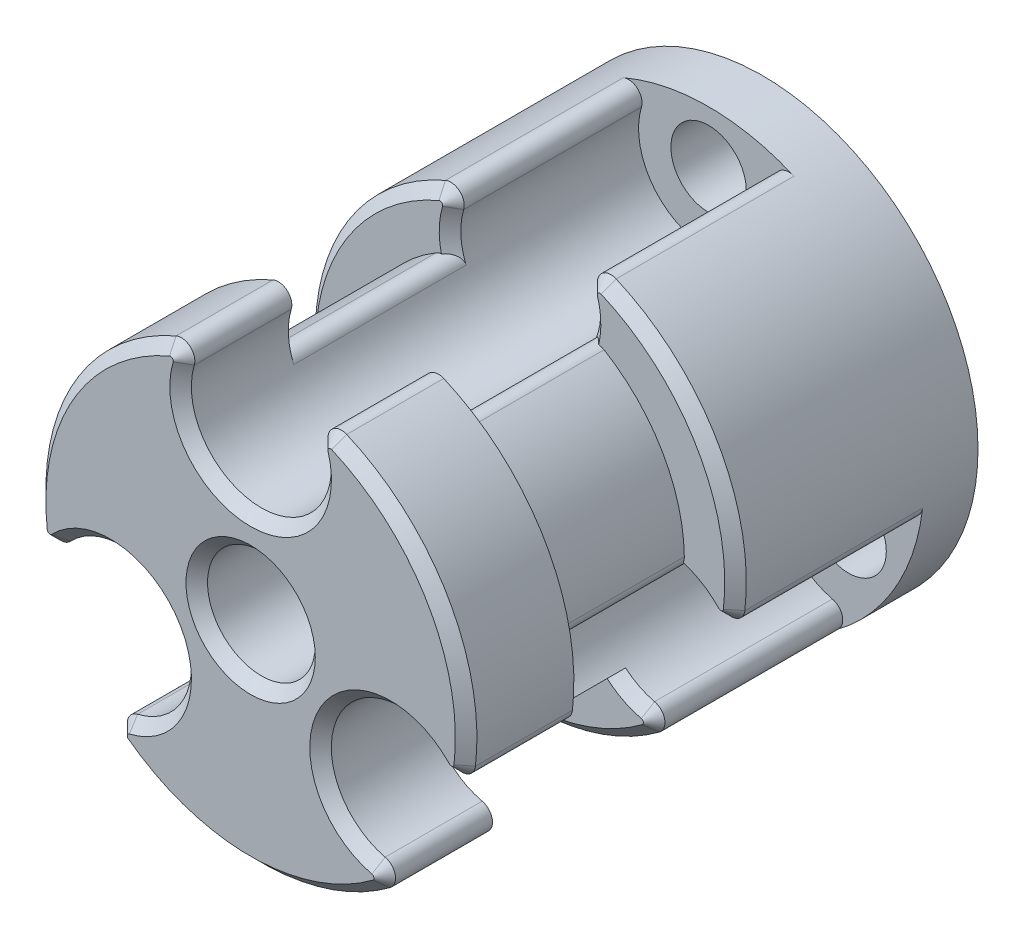
SolidWorks part; units mm, degrees
ref_plane "前视基准面" through (0, 0, 0) normal (0, 0, 1) x (1, 0, 0)
ref_plane "上视基准面" through (0, 0, 0) normal (0, 1, 0) x (1, 0, 0)
ref_plane "右视基准面" through (0, 0, 0) normal (1, 0, 0) x (0, 0, -1)
other "Configuration Table"
sketch "Sketch2" plane through (0, 0, 0) normal (0, 0, 1) x (1, 0, 0)
  circle A0 centre (0, 0) radius 8
  circle A1 centre (0, 0) radius 2
  circle A3 centre (0, 6) radius 1.4
  circle A5 centre (5.1962, -3) radius 1.4
  circle A6 centre (-5.1962, -3) radius 1.4
  point P11 (0, 0)
  dimension "D1" = 16
  dimension "D2" = 4
  dimension "D3" = 2.8
  dimension "D4" = 6
  dimension "D5" = 3
extrude "Boss-Extrude1" add sketch "Sketch2" along normal blind 9
sketch "Sketch3" plane through (0, 0, 9) normal (0, 0, 1) x (1, 0, 0)
  circle A0 centre (0, 6) radius 2.6
  circle A1 centre (5.1962, -3) radius 2.6
  circle A2 centre (-5.1962, -3) radius 2.6
  point P8 (0, 0)
  dimension "D1" = 5.2
  dimension "D2" = 3
extrude "Cut-Extrude1" cut sketch "Sketch3" against normal blind 7
fillet "Fillet1" radius 0.5 6 edges at (1.9045, 7.77, 5.5) (-1.9045, 7.77, 5.5) (-5.7768, -5.5343, 5.5) (-7.6813, -2.2357, 5.5) (5.7768, -5.5343, 5.5) (7.6813, -2.2357, 5.5)
sketch "Sketch4" plane through (0, 0, 9) normal (0, 0, 1) x (1, 0, 0)
  arc A0 (6.0749, -0.553) -> (2.5585, 5.5375) centre (0, 0) ccw
  arc A1 (-2.4914, 6.7437) -> (2.4914, 6.7437) centre (0, 6) ccw construction
  arc A2 (-4.5945, -5.5294) -> (-7.0859, -1.2142) centre (-5.1962, -3) ccw construction
  arc A3 (7.0859, -1.2142) -> (4.5945, -5.5294) centre (5.1962, -3) ccw construction
  arc A4 (-2.5585, 5.5375) -> (2.5585, 5.5375) centre (0, 6) ccw
  arc A5 (-3.5163, -4.9845) -> (-6.0749, -0.553) centre (-5.1962, -3) ccw
  arc A6 (6.0749, -0.553) -> (3.5163, -4.9845) centre (5.1962, -3) ccw
  arc A7 (-3.5163, -4.9845) -> (3.5163, -4.9845) centre (0, 0) ccw
  arc A8 (-2.5585, 5.5375) -> (-6.0749, -0.553) centre (0, 0) ccw
  circle A9 centre (0, 0) radius 2
  dimension "D1" = 12.2
extrude "Boss-Extrude2" add sketch "Sketch4" along normal blind 6
sketch "Sketch5" plane through (0, 0, 15) normal (0, 0, 1) x (1, 0, 0)
  arc A0 (7.9459, -0.9289) -> (3.1685, 7.3458) centre (0, 0) ccw
  arc A1 (-4.5945, -5.5294) -> (-4.7774, -6.4169) centre (-4.4788, -6.0159) ccw construction
  arc A2 (-4.5945, -5.5294) -> (-3.5163, -4.9845) centre (-5.1962, -3) ccw construction
  arc A3 (-3.5163, -4.9845) -> (-6.0749, -0.553) centre (-5.1962, -3) ccw construction
  arc A4 (-6.0749, -0.553) -> (-7.0859, -1.2142) centre (-5.1962, -3) ccw construction
  arc A5 (-7.9459, -0.9289) -> (-7.0859, -1.2142) centre (-7.4493, -0.8708) ccw construction
  arc A6 (-2.4914, 6.7437) -> (-3.1685, 7.3458) centre (-2.9705, 6.8867) ccw construction
  arc A7 (-2.4914, 6.7437) -> (-2.5585, 5.5375) centre (0, 6) ccw construction
  arc A8 (3.1685, 7.3458) -> (2.4914, 6.7437) centre (2.9705, 6.8867) ccw construction
  arc A9 (2.5585, 5.5375) -> (2.4914, 6.7437) centre (0, 6) ccw construction
  arc A10 (-2.5585, 5.5375) -> (2.5585, 5.5375) centre (0, 6) ccw construction
  arc A11 (7.0859, -1.2142) -> (6.0749, -0.553) centre (5.1962, -3) ccw construction
  arc A12 (7.0859, -1.2142) -> (7.9459, -0.9289) centre (7.4493, -0.8708) ccw construction
  arc A13 (3.5163, -4.9845) -> (4.5945, -5.5294) centre (5.1962, -3) ccw construction
  arc A14 (6.0749, -0.553) -> (3.5163, -4.9845) centre (5.1962, -3) ccw construction
  arc A15 (4.7774, -6.4169) -> (4.5945, -5.5294) centre (4.4788, -6.0159) ccw construction
  arc A16 (-4.5945, -5.5294) -> (-4.7774, -6.4169) centre (-4.4788, -6.0159) ccw
  arc A17 (-4.5945, -5.5294) -> (-3.5163, -4.9845) centre (-5.1962, -3) ccw
  arc A18 (-3.5163, -4.9845) -> (-6.0749, -0.553) centre (-5.1962, -3) ccw
  arc A19 (-6.0749, -0.553) -> (-7.0859, -1.2142) centre (-5.1962, -3) ccw
  arc A20 (-7.9459, -0.9289) -> (-7.0859, -1.2142) centre (-7.4493, -0.8708) ccw
  arc A21 (-2.4914, 6.7437) -> (-3.1685, 7.3458) centre (-2.9705, 6.8867) ccw
  arc A22 (-2.4914, 6.7437) -> (-2.5585, 5.5375) centre (0, 6) ccw
  arc A23 (3.1685, 7.3458) -> (2.4914, 6.7437) centre (2.9705, 6.8867) ccw
  arc A24 (2.5585, 5.5375) -> (2.4914, 6.7437) centre (0, 6) ccw
  arc A25 (-2.5585, 5.5375) -> (2.5585, 5.5375) centre (0, 6) ccw
  arc A26 (7.0859, -1.2142) -> (6.0749, -0.553) centre (5.1962, -3) ccw
  arc A27 (7.0859, -1.2142) -> (7.9459, -0.9289) centre (7.4493, -0.8708) ccw
  arc A28 (3.5163, -4.9845) -> (4.5945, -5.5294) centre (5.1962, -3) ccw
  arc A29 (6.0749, -0.553) -> (3.5163, -4.9845) centre (5.1962, -3) ccw
  arc A30 (4.7774, -6.4169) -> (4.5945, -5.5294) centre (4.4788, -6.0159) ccw
  arc A31 (-4.7774, -6.4169) -> (4.7774, -6.4169) centre (0, 0) ccw
  arc A32 (-3.1685, 7.3458) -> (-7.9459, -0.9289) centre (0, 0) ccw
  circle A33 centre (0, 0) radius 2
extrude "Boss-Extrude3" add sketch "Sketch5" along normal blind 4
chamfer "Chamfer1" distance 0.4 angle 45 28 edges at (2, 0, 19) (-7.6067, -1.3454, 19) (-6.9282, 4, 19) (-2.6382, 7.2603, 19) (0, 3.4, 19) (2.6382, 7.2603, 19) (6.9282, 4, 19) (7.6067, -1.3454, 19) (2.9445, -1.7, 19) (4.9685, -5.9149, 19) (0, -8, 19) (-4.9685, -5.9149, 19) (-2.9445, -1.7, 19) (-2.596, 6.1445, 9) (-6.6193, -0.8241, 9) (-2.6382, 7.2603, 9) (-7.6067, -1.3454, 9) (-6.9282, 4, 9) (6.6193, -0.8241, 9) (2.596, 6.1445, 9) (7.6067, -1.3454, 9) (2.6382, 7.2603, 9) (6.9282, 4, 9) (-4.0233, -5.3205, 9) (4.0233, -5.3205, 9) (-4.9685, -5.9149, 9) (4.9685, -5.9149, 9) (0, -8, 9)
fillet "Fillet2" radius 0.5 5 edges at (-3.5163, -4.9845, 11.8) (-6.0749, -0.553, 11.8) (2.5585, 5.5375, 11.8) (-2.5585, 5.5375, 11.8) (6.0749, -0.553, 11.8)
